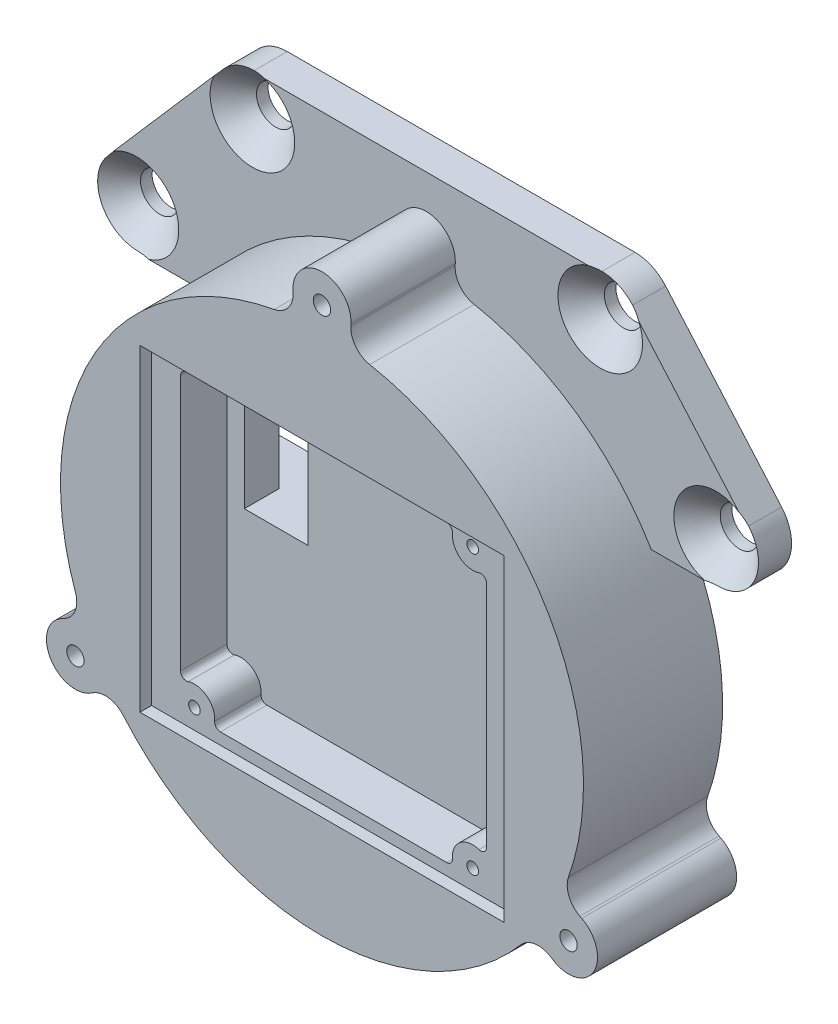
SolidWorks part; units mm, degrees
ref_plane "Спереди" through (0, 0, 0) normal (0, 0, 1) x (1, 0, 0)
ref_plane "Сверху" through (0, 0, 0) normal (0, 1, 0) x (1, 0, 0)
ref_plane "Справа" through (0, 0, 0) normal (1, 0, 0) x (0, 0, -1)
sketch "Эскиз1" plane through (0, 0, 0) normal (0, 0, 1) x (1, 0, 0)
  line L1 (-15.5, -13.5) -> (15.5, -13.5) construction
  line L2 (-15.5, -13.5) -> (-15.5, 13.5) construction
  line L3 (-15.5, 13.5) -> (15.5, 13.5) construction
  line L4 (15.5, -13.5) -> (15.5, 13.5) construction
  line L5 (-15.5, -13.5) -> (15.5, 13.5) construction
  line L6 (-15.5, 13.5) -> (15.5, -13.5) construction
  circle A0 centre (0, 0) radius 20.5548 construction
  circle A1 centre (0, 0) radius 22.5548
  point P0 (0, 0)
  dimension "D3" = 2
  dimension "D4" = 45.1096
  dimension "D1" = 31
  dimension "D2" = 27
extrude "основание" add sketch "Эскиз1" along normal blind 6
sketch "Эскиз2" plane through (0, 0, 6) normal (0, 0, 1) x (1, 0, 0)
  line L1 (-15.7, -13.7) -> (15.7, -13.7)
  line L2 (-15.7, -13.7) -> (-15.7, 13.7)
  line L3 (-15.7, 13.7) -> (15.7, 13.7)
  line L4 (15.7, -13.7) -> (15.7, 13.7)
  line L5 (-15.7, -13.7) -> (15.7, 13.7) construction
  line L6 (-15.7, 13.7) -> (15.7, -13.7) construction
  point P0 (0, 0)
  dimension "D1" = 31.4
  dimension "D2" = 27.4
extrude "углубление для платы" cut sketch "Эскиз2" against normal blind 5
sketch "Эскиз3" plane through (0, 0, 1) normal (0, 0, 1) x (1, 0, 0)
  line L1 (-12, -12) -> (12, -12) construction
  line L2 (-12, -12) -> (-12, 12) construction
  line L3 (-12, 12) -> (12, 12) construction
  line L4 (12, -12) -> (12, 12) construction
  line L5 (-12, -12) -> (12, 12) construction
  line L6 (-12, 12) -> (12, -12) construction
  circle A0 centre (-12, 12) radius 1.75 construction
  circle A1 centre (-12, -12) radius 1.75
  circle A2 centre (12, -12) radius 1.75
  circle A3 centre (12, 12) radius 1.75
  circle A4 centre (12, 12) radius 0.5
  circle A5 centre (12, -12) radius 0.5
  circle A6 centre (-12, -12) radius 0.5
  circle A7 centre (-12, 12) radius 0.5 construction
  point P0 (0, 0)
  dimension "D2" = 3.5
  dimension "D3" = 1
  dimension "D1" = 24
extrude "крепежные стойки" add sketch "Эскиз3" along normal blind 4
sketch "Эскиз4" plane through (0, 0, 1) normal (0, 0, 1) x (1, 0, 0)
  line L0 (15.7, 13.7) -> (12.4153, 13.7) construction
  line L1 (-11.7, 1) -> (-6.2, 1)
  line L2 (-11.7, 1) -> (-11.7, 11.5)
  line L3 (-11.7, 11.5) -> (-6.2, 11.5)
  line L4 (-6.2, 1) -> (-6.2, 11.5)
  line L5 (-11.7, 1) -> (-6.2, 11.5) construction
  line L6 (-11.7, 11.5) -> (-6.2, 1) construction
  line L7 (-15.7, 13.7) -> (-15.7, -13.7) construction
  point P0 (-8.95, 6.25)
  dimension "D1" = 7.45
  dimension "D2" = 6.75
  dimension "D3" = 5.5
  dimension "D4" = 10.5
extrude "отверстие для usb" cut sketch "Эскиз4" against normal through all
sketch "Эскиз5" plane through (0, 0, 1) normal (0, 0, 1) x (1, 0, 0)
  line L1 (15.7, -13.7) -> (-15.7, -13.7)
  line L2 (15.7, -13.7) -> (15.7, 13.7)
  line L3 (15.7, 13.7) -> (-15.7, 13.7)
  line L4 (-15.7, -13.7) -> (-15.7, 13.7)
  line L5 (15.7, -13.7) -> (-15.7, 13.7) construction
  line L6 (15.7, 13.7) -> (-15.7, -13.7) construction
  line L7 (13.2, -12.7) -> (-13.2, -12.7)
  line L8 (13.2, -12.7) -> (13.2, 12.7)
  line L9 (13.2, 12.7) -> (-13.2, 12.7)
  line L10 (-13.2, -12.7) -> (-13.2, 12.7)
  line L11 (13.2, -12.7) -> (-13.2, 12.7) construction
  line L12 (13.2, 12.7) -> (-13.2, -12.7) construction
  point P0 (0, 0)
  point P7 (0, 0)
  dimension "D1" = 1
  dimension "D2" = 2.5
extrude "бортики" add sketch "Эскиз5" along normal blind 4
fillet "Скругление1" radius 0.5 7 edges at (13.2, -10.7262, 3) (10.3961, -12.7, 3) (-13.2, -10.7262, 3) (-10.3961, -12.7, 3) (13.2, 10.7262, 3) (10.3961, 12.7, 3) (-13.2, 12.7, 3)
sketch "Эскиз6" plane through (0, 0, 0) normal (0, 0, -1) x (-1, 0, 0)
  line L1 (6.2, 11.5) -> (11.7, 11.5)
  line L2 (6.2, 11.5) -> (6.2, 1)
  line L3 (6.2, 1) -> (11.7, 1)
  line L4 (11.7, 11.5) -> (11.7, 1)
  circle A0 centre (0, 0) radius 22.5548
  circle A1 centre (0, 0) radius 22.5548 construction
extrude "сплошная утолщаем к нижнему этажу" add sketch "Эскиз6" along normal blind 6
sketch "Эскиз7" plane through (0, 0, -6) normal (0, 0, -1) x (-1, 0, 0)
  line L0 (11.7, 11.5) -> (11.7, 1)
  line L1 (11.7, 11.5) -> (22.5326, 11.5)
  line L2 (11.7, 1) -> (22.5326, 1)
  line L3 (22.5326, 11.5) -> (22.5326, 1)
  line L4 (11.7, 1) -> (11.7, 11.5) construction
  circle A1 centre (0, 0) radius 22.5548 construction
extrude "сплошная паз для проводов" cut sketch "Эскиз7" against normal blind 4
sketch "Эскиз8" plane through (0, 0, -6) normal (0, 0, -1) x (-1, 0, 0)
  line L0 (-15, 26.5) -> (15, 26.5) construction
  line L1 (0, 26.5) -> (0, 15) construction
  line L2 (-25, 15) -> (25, 15) construction
  line L3 (-25, 11.5) -> (-19.4028, 11.5)
  line L6 (19.4028, 11.5) -> (6.2, 11.5) construction
  line L7 (-27.6411, 17.2966) -> (-17.6411, 28.7966)
  line L8 (-15, 30) -> (15, 30)
  line L9 (17.6411, 28.7966) -> (27.6411, 17.2966)
  line L10 (25, 11.5) -> (19.4028, 11.5)
  line L11 (19.4028, 11.5) -> (11.7, 11.5) construction
  circle A0 centre (-15, 26.5) radius 1.65
  circle A1 centre (15, 26.5) radius 1.65
  circle A2 centre (25, 15) radius 1.65
  circle A3 centre (-25, 15) radius 1.65
  arc A4 (19.4028, 11.5) -> (22.5326, 1) centre (0, 0) ccw construction
  arc A5 (17.6411, 28.7966) -> (15, 30) centre (15, 26.5) ccw
  arc A6 (-15, 30) -> (-17.6411, 28.7966) centre (-15, 26.5) ccw
  arc A7 (-27.6411, 17.2966) -> (-25, 11.5) centre (-25, 15) ccw
  arc A8 (25, 11.5) -> (27.6411, 17.2966) centre (25, 15) ccw
  arc A9 (19.4028, 11.5) -> (-19.4028, 11.5) centre (0, 0) ccw
  dimension "D1" = 3.3
  dimension "D5" = 7
  dimension "D2" = 30
  dimension "D3" = 11.5
  dimension "D4" = 50
extrude "крепление к этажу" add sketch "Эскиз8" against normal blind 3
chamfer "Фаска1" distance 2 angle 45 4 edges at (-26.65, 15, -3) (-16.65, 26.5, -3) (23.35, 15, -3) (13.35, 26.5, -3)
sketch "Эскиз14" plane through (0, 0, 6) normal (0, 0, 1) x (1, 0, 0)
  line L0 (21.2651, -12.2774) -> (0, 0) construction
  line L1 (0, 0) -> (-21.2651, -12.2774) construction
  line L2 (0, 0) -> (0, 24.5548) construction
  line L3 (-22.4032, -10.0515) -> (-20.62, -9.1397)
  line L4 (-19.9065, -14.376) -> (-18.2252, -13.2876)
  circle A0 centre (0, 0) radius 24.5548 construction
  circle A1 centre (21.2651, -12.2774) radius 2.5 construction
  arc A2 (-22.4032, -10.0515) -> (-19.9065, -14.376) centre (-21.2651, -12.2774) ccw
  circle A3 centre (0, 24.5548) radius 2.5 construction
  arc A4 (19.4028, 11.5) -> (-19.4028, 11.5) centre (0, 0) ccw construction
  circle A6 centre (-21.2651, -12.2774) radius 0.75
  arc A7 (-20.62, -9.1397) -> (-18.2252, -13.2876) centre (0, 0) ccw
  circle A10 centre (0, 0) radius 22.5548 construction
  dimension "D3" = 5
  dimension "D4" = 2
  dimension "D5" = 1.5
  dimension "D1" = 120
  dimension "D2" = 120
extrude "крепление защиты" add sketch "Эскиз14" against normal up to surface (12 mm away) up to face at (-0.7072, 14.2443, -6)
fillet "Скругление3" radius 2 2 edges at (-20.62, -9.1397, 0) (-18.2252, -13.2876, 0)
pattern_circular "Круговой массив1" count 3 over 360 about axis through (0, 0, 6) along (0, 0, -1) of "крепление защиты", "Скругление3"
